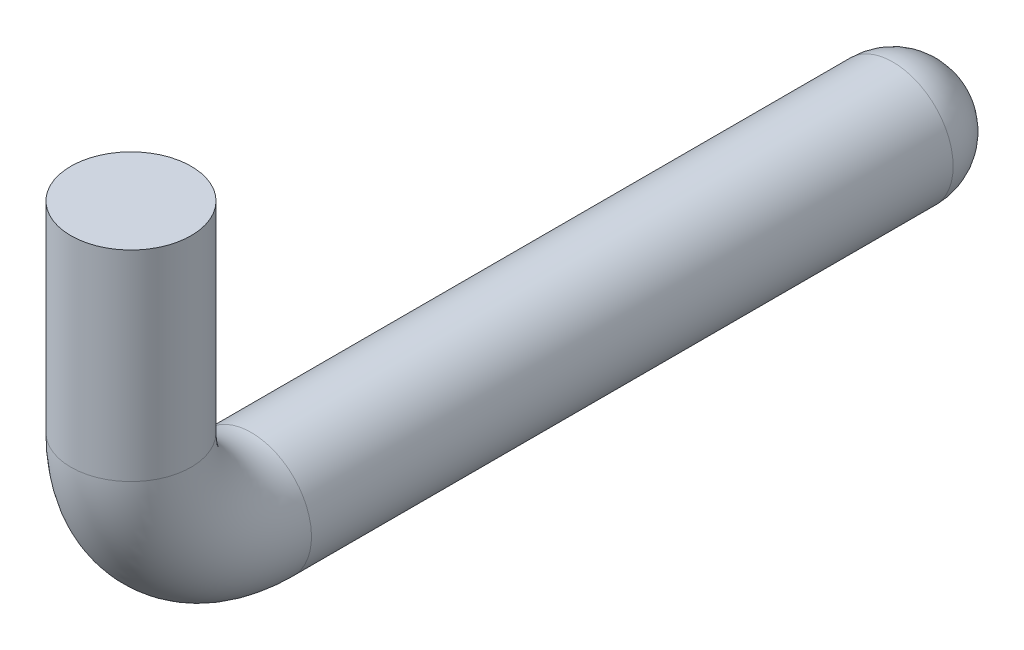
SolidWorks part; units mm, degrees
ref_plane "Alzado" through (0, 0, 0) normal (0, 0, 1) x (1, 0, 0)
ref_plane "Planta" through (0, 0, 0) normal (0, 1, 0) x (1, 0, 0)
ref_plane "Vista lateral" through (0, 0, 0) normal (1, 0, 0) x (0, 0, -1)
sketch "Croquis1" plane through (0, 0, 0) normal (1, 0, 0) x (0, 0, -1)
  line L0 (0, 0) -> (0, -0.25)
  line L1 (0.15, -0.4) -> (0.95, -0.4)
  arc A0 (0, -0.25) -> (0.15, -0.4) centre (0.15, -0.25) ccw
  point P6 (0, -0.4)
  dimension "D3" = 0.15
  dimension "D1" = 0.4
  dimension "D2" = 0.95
sketch "Croquis2" plane through (0, 0, 0) normal (0, 1, 0) x (1, 0, 0)
  circle A0 centre (0, 0) radius 0.075
  dimension "D1" = 0.15
sweep "Barrer1" add profiles "Croquis2" path "Croquis1"
dome "Cúpula1" faces to dome 1 distance 0.075 reverse direction no elliptical dome no face at (0, -0.475, -0.95) parameters "D1"=0.075
